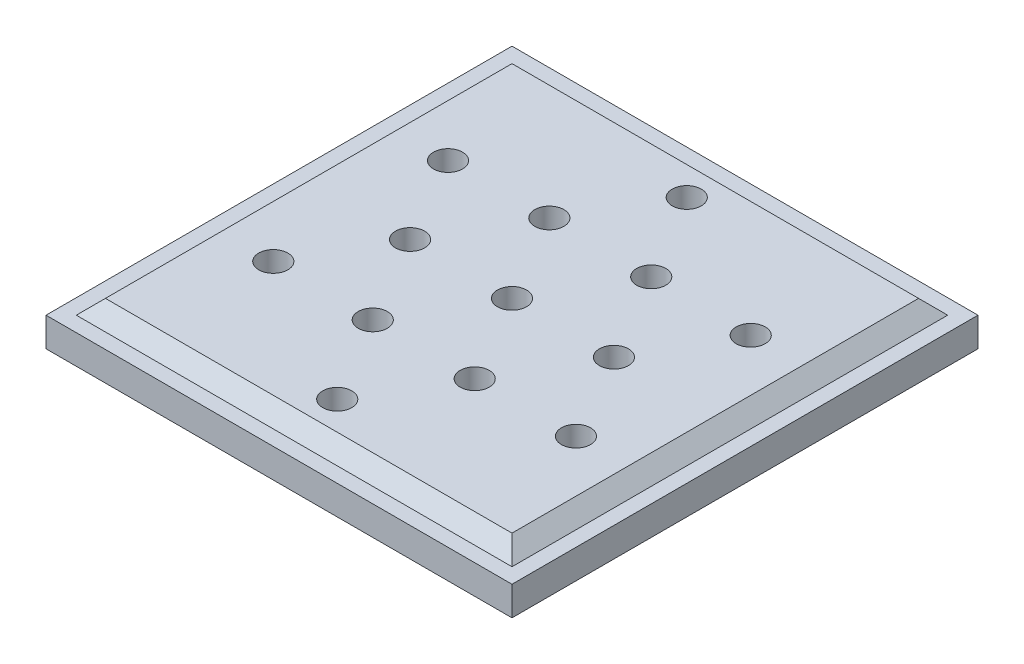
SolidWorks part; units mm, degrees
ref_plane "Front Plane" through (0, 0, 0) normal (0, 0, 1) x (1, 0, 0)
ref_plane "Top Plane" through (0, 0, 0) normal (0, 1, 0) x (1, 0, 0)
ref_plane "Right Plane" through (0, 0, 0) normal (1, 0, 0) x (0, 0, -1)
sketch "Sketch1" plane through (0, 0, 0) normal (0, 1, 0) x (1, 0, 0)
  line L1 (-50.8, 50.8) -> (50.8, 50.8)
  line L2 (-50.8, 50.8) -> (-50.8, -50.8)
  line L3 (-50.8, -50.8) -> (50.8, -50.8)
  line L4 (50.8, 50.8) -> (50.8, -50.8)
  line L5 (-50.8, 50.8) -> (50.8, -50.8) construction
  line L6 (-50.8, -50.8) -> (50.8, 50.8) construction
  point P0 (0, 0)
  dimension "D1" = 101.6
  dimension "D2" = 101.6
extrude "Boss-Extrude1" add sketch "Sketch1" along normal blind 9.525
sketch "Sketch2" plane through (0, 9.525, 0) normal (0, 1, 0) x (1, 0, 0)
  line L0 (-50.8, 50.8) -> (-50.8, -50.8) construction
  line L1 (-47.498, 47.498) -> (47.498, 47.498)
  line L2 (-47.498, 47.498) -> (-47.498, -47.498)
  line L3 (-47.498, -47.498) -> (47.498, -47.498)
  line L4 (47.498, 47.498) -> (47.498, -47.498)
  line L5 (-47.498, 47.498) -> (47.498, -47.498) construction
  line L6 (-47.498, -47.498) -> (47.498, 47.498) construction
  line L7 (50.8, 50.8) -> (-50.8, 50.8) construction
  point P0 (0, 0)
  dimension "D1" = 3.302
  dimension "D2" = 3.302
extrude "Cut-Extrude1" cut sketch "Sketch2" against normal blind 3.175 flip side to cut
chamfer "Chamfer1" distance 3.175 angle 45 4 edges at (47.498, 9.525, 0) (0, 9.525, -47.498) (-47.498, 9.525, 0) (0, 9.525, 47.498)
sketch "Sketch3" plane through (0, 9.525, 0) normal (0, 1, 0) x (1, 0, 0)
  line L0 (0, 50.8) -> (0, -50.8) construction
  line L1 (50.8, 50.8) -> (-50.8, 50.8) construction
  line L2 (-50.8, -50.8) -> (50.8, -50.8) construction
  line L3 (50.8, 0) -> (-50.8, 0) construction
  line L4 (50.8, -50.8) -> (50.8, 50.8) construction
  line L5 (-50.8, 50.8) -> (-50.8, -50.8) construction
  line L6 (0, 38.1) -> (-32.9956, -19.05) construction
  line L7 (-32.9956, -19.05) -> (32.9956, -19.05) construction
  line L8 (32.9956, -19.05) -> (0, 38.1) construction
  line L9 (-32.9956, 19.05) -> (0, -38.1) construction
  line L10 (0, -38.1) -> (32.9956, 19.05) construction
  line L11 (-32.9956, 19.05) -> (32.9956, 19.05) construction
  circle A0 centre (0, 0) radius 38.1 construction
  circle A1 centre (0, 38.1) radius 3.175
  circle A2 centre (32.9956, 19.05) radius 3.175
  circle A3 centre (32.9956, -19.05) radius 3.175
  circle A4 centre (0, -38.1) radius 3.175
  circle A5 centre (-32.9956, -19.05) radius 3.175
  circle A6 centre (-32.9956, 19.05) radius 3.175
  circle A7 centre (0, 0) radius 22.225 construction
  circle A8 centre (22.225, 0) radius 3.175
  circle A9 centre (11.1125, -19.2474) radius 3.175
  circle A10 centre (-11.1125, -19.2474) radius 3.175
  circle A11 centre (-22.225, 0) radius 3.175
  circle A12 centre (-11.1125, 19.2474) radius 3.175
  circle A13 centre (11.1125, 19.2474) radius 3.175
  circle A14 centre (0, 0) radius 3.175
  point P29 (0, 0)
  point P42 (0, 0)
  dimension "D1" = 76.2
  dimension "D2" = 6.35
  dimension "D4" = 44.45
  dimension "D5" = 6.35
  dimension "D7" = 6.35
  dimension "D3" = 6
  dimension "D6" = 6
extrude "Cut-Extrude2" cut sketch "Sketch3" against normal up to next
equation "\"D4@Sketch3\"=\"D1@Sketch3\"-1.25in"
